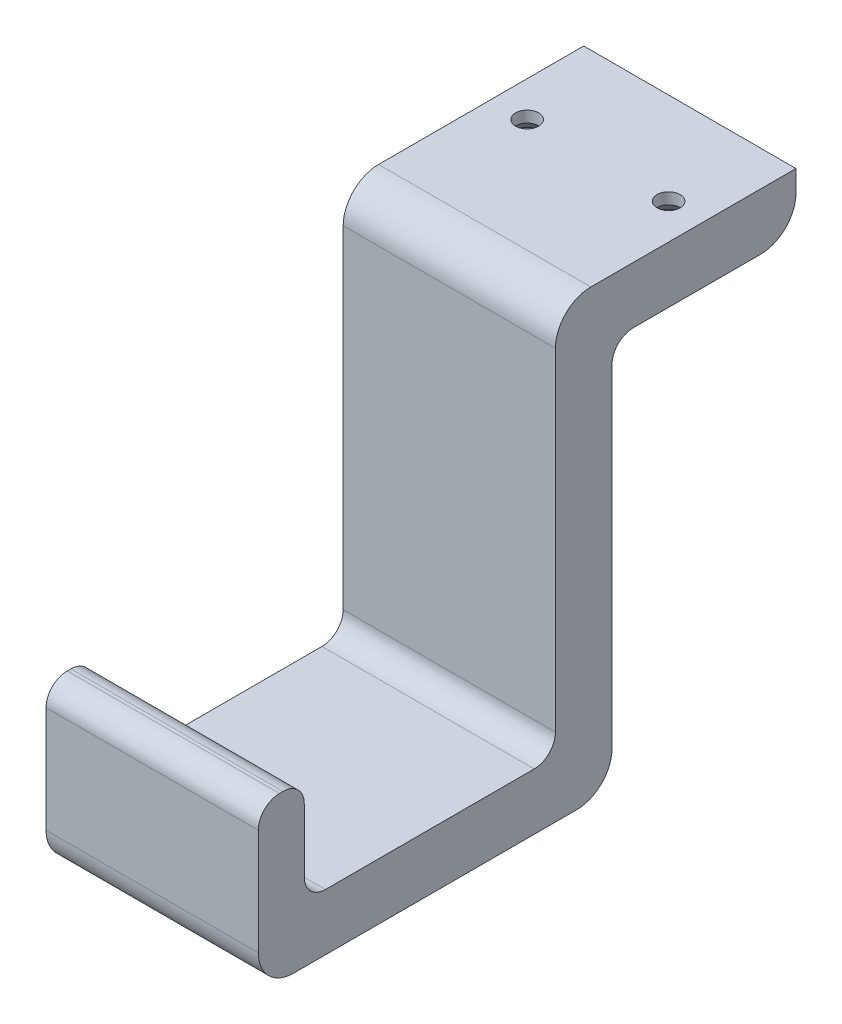
SolidWorks part; units mm, degrees
material "PLA Polyacetic Acid"
ref_plane "Front Plane" through (0, 0, 0) normal (0, 0, 1) x (1, 0, 0)
ref_plane "Top Plane" through (0, 0, 0) normal (0, 1, 0) x (1, 0, 0)
ref_plane "Right Plane" through (0, 0, 0) normal (1, 0, 0) x (0, 0, -1)
sketch "Sketch1" plane through (0, 0, 0) normal (1, 0, 0) x (0, 0, -1)
  line L0 (-50, 0) -> (0, 0)
  line L1 (0, 0) -> (0, 55)
  line L2 (0, 55) -> (26, 55)
  line L3 (-50, 0) -> (-50, 23)
  line L4 (-50, 23) -> (-43.5, 23)
  line L5 (-43.5, 23) -> (-43.5, 8)
  line L6 (-43.5, 8) -> (-8, 8)
  line L7 (-8, 8) -> (-8, 63)
  line L8 (-8, 63) -> (26, 63)
  line L9 (26, 63) -> (26, 55)
  line L10 (-8, 55) -> (0, 55) construction
  line L11 (0, 63) -> (0, 55) construction
  line L12 (-8, 8) -> (-8, 0) construction
  dimension "D1" = 50
  dimension "D2" = 63
  dimension "D3" = 26
  dimension "D4" = 15
  dimension "D5" = 6.5
  dimension "D6" = 8
  dimension "D7" = 34
extrude "Boss-Extrude1" add sketch "Sketch1" along normal mid plane 30
fillet "Fillet1" radius 5 4 edges at (0, 63, 8) (0, 0, 0) (0, 0, 50) (0, 55, -26)
fillet "Fillet2" radius 3 5 edges at (0, 23, 43.5) (0, 23, 50) (0, 8, 8) (0, 8, 43.5) (0, 55, 0)
hole_wizard "CSK for #4 Flat Head Machine Screw2" positions "Sketch5" profile "Sketch6" countersink size "#4" standard "ANSI Inch" end condition up to next
sketch "Sketch5" plane through (0, 55, 0) normal (0, -1, 0) x (1, 0, 0)
  line L0 (0, 0) -> (0, -26) construction
  line L1 (15, 0) -> (-15, 0) construction
  line L2 (15, -26) -> (-15, -26) construction
  line L5 (0, -13) -> (-10, -13) construction
  point P0 (-10, -13)
  point P15 (10, -13)
  dimension "D1" = 20
sketch "Sketch6" plane through (-10, 55, -13) normal (1, 0, 0) x (0, 0, -1)
  line L0 (0, 0) -> (0, 8)
  line L1 (0, 8) -> (1.6319, 8)
  line L2 (1.6319, 8) -> (1.6319, 6.4098)
  line L3 (1.6319, 6.4098) -> (2.8575, 5)
  line L4 (2.8575, 5) -> (2.8575, 0)
  line L6 (2.8575, 0) -> (0, 0)
  line L7 (-1.632, 6.4098) -> (-2.8575, 5) construction
  line L11 (0, -6.35) -> (0, 107.95) construction
  dimension "Thru Hole Dia." = 3.2639
  dimension "Thru Hole Depth" = 8
  dimension "C'Sink Dia." = 5.715
  dimension "C'Sink Angle" = 82
  dimension "Head Clearance" = 5
